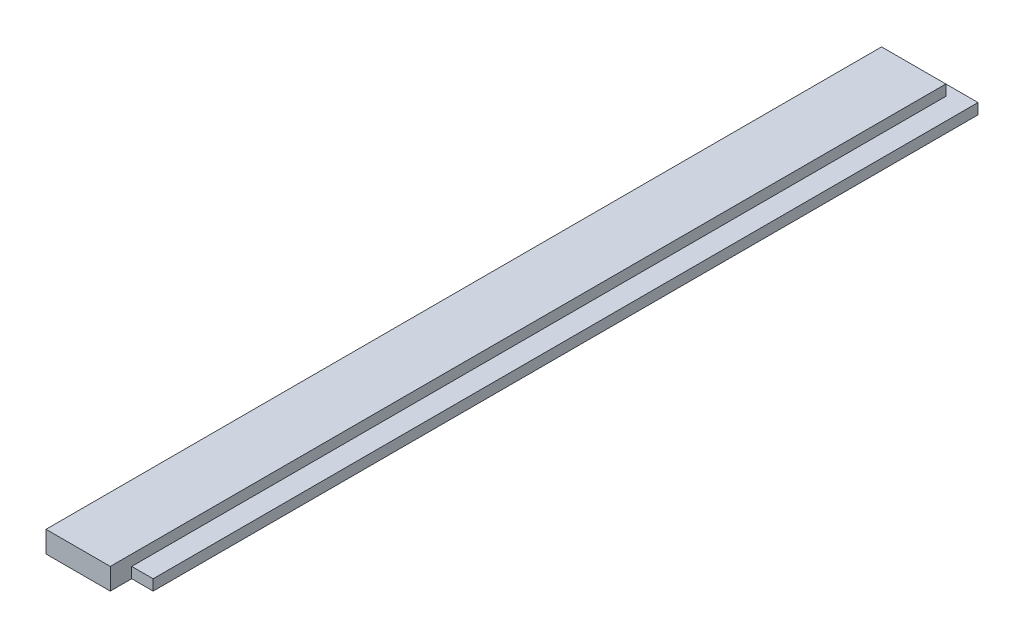
SolidWorks part; units mm, degrees
ref_plane "Front Plane" through (0, 0, 0) normal (0, 0, 1) x (1, 0, 0)
ref_plane "Top Plane" through (0, 0, 0) normal (0, 1, 0) x (1, 0, 0)
ref_plane "Right Plane" through (0, 0, 0) normal (1, 0, 0) x (0, 0, -1)
sketch "Sketch1" plane through (0, 0, 0) normal (0, 0, 1) x (1, 0, 0)
  line L0 (0, 12.7) -> (38.1, 12.7)
  line L1 (38.1, 12.7) -> (38.1, 6.35)
  line L2 (38.1, 6.35) -> (50.8, 6.35)
  line L3 (50.8, 6.35) -> (50.8, 0)
  line L4 (50.8, 0) -> (0, 0)
  line L5 (0, 0) -> (0, 12.7)
  dimension "D1" = 6.35
  dimension "D2" = 6.35
  dimension "D3" = 50.8
  dimension "D4" = 12.7
extrude "Boss-Extrude1" add sketch "Sketch1" along normal blind 501.65
sketch "Sketch3" plane through (0, 12.7, 0) normal (0, 1, 0) x (1, 0, 0)
  line L0 (38.1, -501.65) -> (38.1, 0) construction
  line L1 (38.1, -6.35) -> (0, -6.35)
  line L2 (38.1, -6.35) -> (38.1, 0)
  line L3 (38.1, 0) -> (0, 0)
  line L4 (0, -6.35) -> (0, 0)
  dimension "D1" = 6.35
extrude "Cut-Extrude1" cut sketch "Sketch3" against normal blind 6.35
sketch "Sketch4" plane through (0, 0, 0) normal (0, -1, 0) x (1, 0, 0)
  line L1 (50.8, 501.65) -> (38.1, 501.65)
  line L2 (50.8, 501.65) -> (50.8, 488.95)
  line L3 (50.8, 488.95) -> (38.1, 488.95)
  line L4 (38.1, 501.65) -> (38.1, 488.95)
  dimension "D1" = 12.7
  dimension "D2" = 12.7
extrude "Cut-Extrude4" cut sketch "Sketch4" against normal through all
